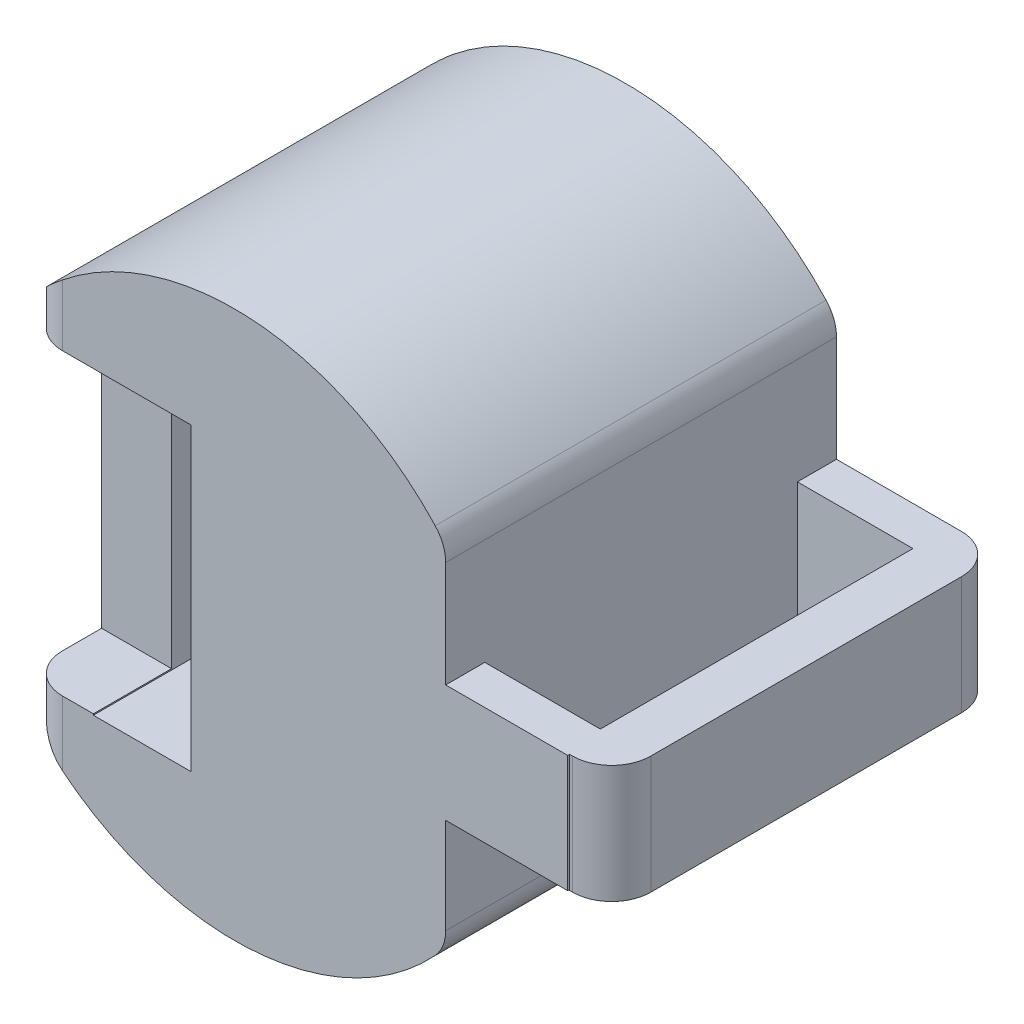
SolidWorks part; units mm, degrees
ref_plane "前基準面" through (0, 0, 0) normal (0, 0, 1) x (1, 0, 0)
ref_plane "上基準面" through (0, 0, 0) normal (0, 1, 0) x (1, 0, 0)
ref_plane "右基準面" through (0, 0, 0) normal (1, 0, 0) x (0, 0, -1)
sketch "草圖1" plane through (0.3827, 0, 0) normal (0, 0, 1) x (1, 0, 0)
  circle A0 centre (-75.5944, 2.55) radius 7
extrude "填料-伸長1" add sketch "草圖1" along normal blind 10 contours A0
ref_plane "平面1" through (0, 0, 9) normal (0, 0, 1) x (1, 0, 0)
sketch "草圖9" plane through (6.1278, 0, 9) normal (0, 0, 1) x (1, 0, 0)
  line L0 (-79.2052, 4.535) -> (-72.0845, 4.535)
  line L1 (-72.0845, 4.535) -> (-72.0845, 0)
  line L2 (-72.0845, 0) -> (-79.2052, 0)
  line L3 (-79.2052, 0) -> (-79.2052, 4.535)
extrude "填料-伸長6" add sketch "草圖9" along normal blind 1
sketch "草圖11" plane through (9.5745, 4.535, 0.4843) normal (0, 1, 0) x (1, 0, 0)
  line L0 (-75.5559, -9) -> (-75.5559, 0)
  line L2 (-75.5559, 0) -> (-76.8136, 0)
  line L3 (-76.8136, 0) -> (-76.8136, -9)
  line L4 (-76.8136, -9) -> (-75.5559, -9)
extrude "填料-伸長7" add sketch "草圖11" against normal blind 4.5 separate body
sketch "草圖12" plane through (-67.2391, 0, 0) normal (-1, 0, 0) x (0, 0, 1)
  line L0 (0.4843, 4.535) -> (0.4843, 0)
  line L1 (0.4843, 4.535) -> (1.4836, 4.535)
  line L2 (1.4836, 4.535) -> (1.4836, 0.035)
  line L3 (0.4843, 0.035) -> (9.4843, 0.035) construction
  line L4 (1.4836, 0.035) -> (0.4843, 0)
extrude "填料-伸長8" add sketch "草圖12" along normal blind 6
fillet "圓角8" radius 1 1 edges at (-65.9814, 2.285, 0.4843)
fillet "圓角9" radius 1 1 edges at (-65.9567, 2.2675, 10)
sketch "草圖13" plane through (0, 0, 0) normal (0, 0, -1) x (-1, 0, 0)
  line L0 (69.8128, 7.0056) -> (69.8128, -1.9056)
  circle A0 centre (75.2117, 2.55) radius 7 construction
  arc A1 (69.8128, 7.0056) -> (69.8128, -1.9056) centre (72.0817, 2.55) ccw
extrude "除料-伸長1" cut sketch "草圖13" against normal blind 10
sketch "草圖14" plane through (-69.8128, 0, 0) normal (1, 0, 0) x (0, 0, -1)
  line L0 (-10, -1.9056) -> (-10, 7.0056) construction
  line L1 (-10, 3.9175) -> (-9, 3.9175)
  line L2 (-10, 3.9175) -> (-10, 0.9175)
  line L3 (-10, 0.9175) -> (-9, 0.9175)
  line L4 (-9, 3.9175) -> (-9, 0.9175)
sketch "草圖15" plane through (-69.8128, 0, 0) normal (1, 0, 0) x (0, 0, -1)
  line L0 (0, -1.9056) -> (0, 7.0056) construction
  line L1 (0, 3.9175) -> (-1, 3.9175)
  line L2 (0, 3.9175) -> (0, 0.9175)
  line L3 (0, 0.9175) -> (-1, 0.9175)
  line L4 (-1, 3.9175) -> (-1, 0.9175)
extrude "填料-伸長9" add sketch "草圖14" along normal blind 3.122 contours L4 L3 L2 L1
extrude "填料-伸長10" add sketch "草圖15" along normal blind 4
sketch "草圖16" plane through (-65.8128, 0, 0) normal (1, 0, 0) x (0, 0, -1)
  line L1 (0, 3.9175) -> (-9.9523, 3.9175)
  line L2 (0, 3.9175) -> (0, 0.9)
  line L3 (0, 0.9) -> (-9.9523, 0.9)
  line L4 (-9.9523, 3.9175) -> (-9.9523, 0.9)
extrude "填料-伸長11" add sketch "草圖16" along normal blind 0.2 and the other way blind 1.0436
fillet "圓角11" radius 1 1 edges at (-65.6128, 2.4088, 0)
fillet "圓角12" radius 1 1 edges at (-65.6128, 2.4088, 9.9523)
fillet "圓角13" radius 1 1 edges at (-69.8128, 7.0056, 5)
fillet "圓角14" radius 1 1 edges at (-69.8128, -1.9056, 5)
sketch "草圖17" plane through (0, 0, 0) normal (0, 0, -1) x (-1, 0, 0)
  line L0 (80.6179, 6.9967) -> (80.6179, -1.8967)
  arc A0 (70.0797, -2.2105) -> (70.0797, 7.3105) centre (75.2117, 2.55) ccw construction
  arc A1 (80.6179, 6.9967) -> (80.6179, -1.8967) centre (76.5896, 2.55) cw
extrude "除料-伸長2" cut sketch "草圖17" against normal blind 10
sketch "草圖18" plane through (0, 0, 0) normal (0, 0, -1) x (-1, 0, 0)
  line L1 (78.8276, -1.2614) -> (76.3276, -1.2614)
  line L2 (78.8276, -1.2614) -> (78.8276, 6.4198)
  line L3 (78.8276, 6.4198) -> (76.3276, 6.4198)
  line L4 (76.3276, -1.2614) -> (76.3276, 6.4198)
extrude "除料-伸長3" cut sketch "草圖18" against normal blind 10
sketch "草圖19" plane through (0, 0, 0) normal (0, 0, -1) x (-1, 0, 0)
  line L0 (78.8276, 6.4198) -> (80.6179, 6.4198)
  line L1 (80.6179, 6.9967) -> (80.6179, -1.8967) construction
  line L2 (80.6179, 6.4198) -> (80.6179, -1.2614)
  line L3 (80.6179, -1.2614) -> (78.8276, -1.2614)
  line L4 (78.8276, -1.2614) -> (78.8276, 6.4198)
extrude "除料-伸長4" cut sketch "草圖19" against normal blind 2
sketch "草圖20" plane through (0, 0, 10) normal (0, 0, 1) x (1, 0, 0)
  line L0 (-80.6179, 6.9967) -> (-80.6179, -1.8967) construction
  line L1 (-78.8276, 6.4198) -> (-80.6179, 6.4198)
  line L2 (-78.8276, 6.4198) -> (-78.8276, -1.2293)
  line L3 (-78.8276, -1.2293) -> (-80.6179, -1.2293)
  line L4 (-80.6179, 6.4198) -> (-80.6179, -1.2293)
extrude "除料-伸長5" cut sketch "草圖20" against normal blind 2
fillet "圓角15" radius 1 1 edges at (-80.6179, 6.7082, 0)
fillet "圓角16" radius 1 1 edges at (-80.6179, 6.7082, 10)
fillet "圓角17" radius 1 1 edges at (-80.6179, -1.5791, 0)
fillet "圓角18" radius 1 1 edges at (-80.6179, -1.563, 10)
